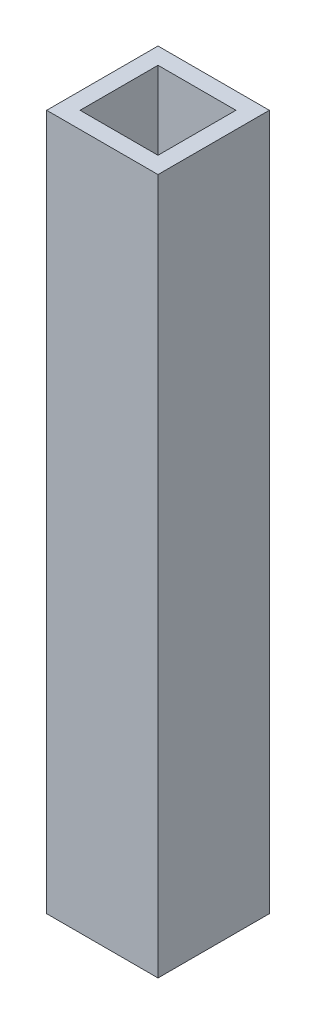
SolidWorks part; units mm, degrees
ref_plane "Front Plane" through (0, 0, 0) normal (0, 0, 1) x (1, 0, 0)
ref_plane "Top Plane" through (0, 0, 0) normal (0, 1, 0) x (1, 0, 0)
ref_plane "Right Plane" through (0, 0, 0) normal (1, 0, 0) x (0, 0, -1)
sketch "Sketch1" plane through (0, 0, 0) normal (0, 0, 1) x (1, 0, 0)
  line L1 (-10, -62.5) -> (10, -62.5)
  line L2 (-10, -62.5) -> (-10, 62.5)
  line L3 (-10, 62.5) -> (10, 62.5)
  line L4 (10, -62.5) -> (10, 62.5)
  line L5 (-10, -62.5) -> (10, 62.5) construction
  line L6 (-10, 62.5) -> (10, -62.5) construction
  point P0 (0, 0)
  dimension "D1" = 125
  dimension "D2" = 20
extrude "Boss-Extrude1" add sketch "Sketch1" along normal blind 20
shell "Shell1" thickness 3 removed face at (0, -62.5, 10) removed face at (0, 62.5, 10)
